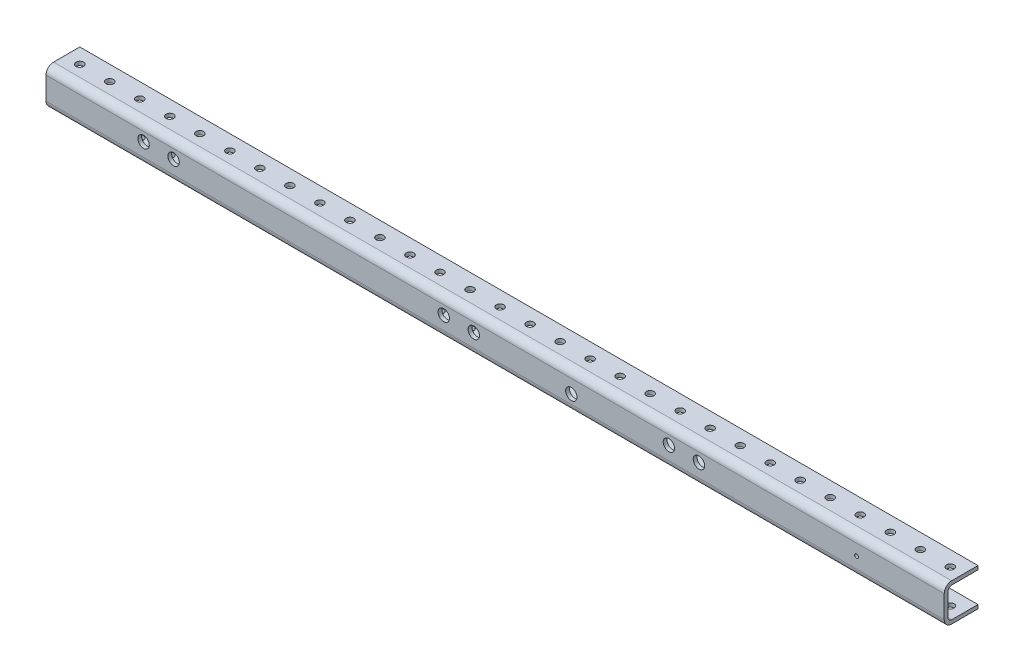
SolidWorks part; units mm, degrees
ref_plane "Front Plane" through (0, 0, 0) normal (0, 0, 1) x (1, 0, 0)
ref_plane "Top Plane" through (0, 0, 0) normal (0, 1, 0) x (1, 0, 0)
ref_plane "Right Plane" through (0, 0, 0) normal (1, 0, 0) x (0, 0, -1)
ref_plane "Plane1" through (0, 0, 3.175) normal (0, 0, 1) x (1, 0, 0)
sketch "Sketch1" plane through (0, 0, 3.175) normal (0, 0, 1) x (1, 0, 0)
  line L0 (872.98, -7.202) -> (872.98, 24.548)
  line L1 (872.98, 24.548) -> (-16.02, 24.548)
  line L2 (-16.02, 24.548) -> (-16.02, -7.202)
  line L3 (-16.02, -7.202) -> (872.98, -7.202)
extrude "Extrude1" add sketch "Sketch1" against normal blind 28.575
sketch "Sketch2" plane through (-16.02, 0, 0) normal (-1, 0, 0) x (0, 0, 1)
  line L0 (-25.4, 21.373) -> (-25.4, -4.027)
  line L1 (-25.4, -4.027) -> (0, -4.027)
  line L2 (0, -4.027) -> (0, 21.373)
  line L3 (0, 21.373) -> (-25.4, 21.373)
extrude "Extrude2" cut sketch "Sketch2" against normal up to next
hole_wizard "Hole1" positions "Sketch4" profile "Sketch3" legacy
sketch "Sketch4" plane through (0, 24.548, 0) normal (0, 1, 0) x (-1, 0, 0)
  point P0 (3.32, -12.7)
sketch "Sketch3" plane through (-3.32, 24.548, -12.7) normal (1, 0, 0) x (0, 0, 1)
  line L0 (0, 0) -> (0, 3.175)
  line L1 (0, 3.175) -> (3.175, 3.175)
  line L2 (3.175, 3.175) -> (3.175, 0)
  line L3 (3.175, 0) -> (0, 0)
  line L4 (0, 110) -> (0, -10) construction
  dimension "Diameter" = 6.35
  dimension "Depth" = 3.175
sketch3d "3DSketch1"
  point P0 (428.6664, 8.6668, -7.2024)
  point P1 (528.6664, 8.6668, -7.2024)
ref_axis "Axis1" through (528.6664, 8.6668, -7.2024) along (-1, 0, 0)
pattern_linear "LPattern1" count 35 spacing 25.4 along (1, 0, 0) of "Hole1"
hole_wizard "Hole2" positions "Sketch6" profile "Sketch5" legacy
sketch "Sketch6" plane through (0, 0, 3.175) normal (0, 0, 1) x (1, 0, 0)
  point P0 (66.53, 10.578)
sketch "Sketch5" plane through (66.53, 10.578, 3.175) normal (1, 0, 0) x (0, -1, 0)
  line L0 (0, 0) -> (0, 3.175)
  line L1 (0, 3.175) -> (4.826, 3.175)
  line L2 (4.826, 3.175) -> (4.826, 0)
  line L3 (4.826, 0) -> (0, 0)
  line L4 (0, 110) -> (0, -10) construction
  dimension "Diameter" = 9.652
  dimension "Depth" = 3.175
sketch3d "3DSketch2"
  point P0 (428.8468, 8.4517, -7.1294)
  point P1 (528.8468, 8.4517, -7.1294)
ref_axis "Axis2" through (528.8468, 8.4517, -7.1294) along (-1, 0, 0)
pattern_linear "LPattern2" count 12 spacing 25.4 along (1, 0, 0) skipping (2, 0), (3, 0), (4, 0), (5, 0), (6, 0), (7, 0), (8, 0), (9, 0) of "Hole2"
hole_wizard "Hole3" positions "Sketch8" profile "Sketch7" legacy
sketch "Sketch8" plane through (0, 0, 3.175) normal (0, 0, 1) x (1, 0, 0)
  point P0 (428.48, 6.768)
sketch "Sketch7" plane through (428.48, 6.768, 3.175) normal (1, 0, 0) x (0, -1, 0)
  line L0 (0, 0) -> (0, 3.175)
  line L1 (0, 3.175) -> (4.826, 3.175)
  line L2 (4.826, 3.175) -> (4.826, 0)
  line L3 (4.826, 0) -> (0, 0)
  line L4 (0, 110) -> (0, -10) construction
  dimension "Diameter" = 9.652
  dimension "Depth" = 3.175
hole_wizard "Hole4" positions "Sketch10" profile "Sketch9" legacy
sketch "Sketch10" plane through (0, 0, 3.175) normal (0, 0, 1) x (1, 0, 0)
  point P0 (511.03, 10.578)
sketch "Sketch9" plane through (511.03, 10.578, 3.175) normal (1, 0, 0) x (0, -1, 0)
  line L0 (0, 0) -> (0, 3.175)
  line L1 (0, 3.175) -> (4.826, 3.175)
  line L2 (4.826, 3.175) -> (4.826, 0)
  line L3 (4.826, 0) -> (0, 0)
  line L4 (0, 110) -> (0, -10) construction
  dimension "Diameter" = 9.652
  dimension "Depth" = 3.175
sketch3d "3DSketch3"
  point P0 (429.3014, 8.4448, -7.1738)
  point P1 (529.3014, 8.4448, -7.1738)
ref_axis "Axis3" through (529.3014, 8.4448, -7.1738) along (-1, 0, 0)
pattern_linear "LPattern3" count 12 spacing 25.4 along (1, 0, 0) skipping (2, 0), (3, 0), (4, 0), (5, 0), (6, 0), (7, 0), (8, 0), (9, 0) of "Hole4"
hole_wizard "Hole5" positions "Sketch12" profile "Sketch11" legacy
sketch "Sketch12" plane through (0, 0, 3.175) normal (0, 0, 1) x (1, 0, 0)
  point P0 (669.78, 8.673)
sketch "Sketch11" plane through (669.78, 8.673, 3.175) normal (1, 0, 0) x (0, -1, 0)
  line L0 (0, 0) -> (0, 3.175)
  line L1 (0, 3.175) -> (1.5875, 3.175)
  line L2 (1.5875, 3.175) -> (1.5875, 0)
  line L3 (1.5875, 0) -> (0, 0)
  line L4 (0, 110) -> (0, -10) construction
  dimension "Diameter" = 3.175
  dimension "Depth" = 3.175
hole_wizard "Hole6" positions "Sketch14" profile "Sketch13" legacy
sketch "Sketch14" plane through (0, -4.027, 0) normal (0, 1, 0) x (-1, 0, 0)
  point P0 (3.32, -12.7)
sketch "Sketch13" plane through (-3.32, -4.027, -12.7) normal (1, 0, 0) x (0, 0, 1)
  line L0 (0, 0) -> (0, 3.175)
  line L1 (0, 3.175) -> (3.175, 3.175)
  line L2 (3.175, 3.175) -> (3.175, 0)
  line L3 (3.175, 0) -> (0, 0)
  line L4 (0, 110) -> (0, -10) construction
  dimension "Diameter" = 6.35
  dimension "Depth" = 3.175
sketch3d "3DSketch4"
  point P0 (428.6444, 8.4444, -7.1991)
  point P1 (528.6444, 8.4444, -7.1991)
ref_axis "Axis4" through (528.6444, 8.4444, -7.1991) along (-1, 0, 0)
pattern_linear "LPattern4" count 35 spacing 25.4 along (1, 0, 0) of "Hole6"
fillet "Fillet1" radius 3.175 1 edges at (428.48, 21.373, 0) tangent propagation no
fillet "Fillet2" radius 3.175 1 edges at (428.48, -4.027, 0) tangent propagation no
fillet "Fillet3" radius 6.35 1 edges at (428.48, -7.202, 3.175) tangent propagation no
fillet "Fillet4" radius 6.35 1 edges at (428.48, 24.548, 3.175) tangent propagation no
sketch "Sketch15" plane through (0, 24.548, 0) normal (0, 1, 0) x (1, 0, 0)
  line L0 (-16.02, 14.2875) -> (743.98, 14.2875) construction
  line L1 (-16.02, 25.4) -> (-16.02, 3.175) construction
  line L3 (743.98, -10.6979) -> (876.3755, -10.6979)
  line L4 (743.98, -10.6979) -> (743.98, 49.9675)
  line L5 (743.98, 49.9675) -> (876.3755, 49.9675)
  line L6 (876.3755, -10.6979) -> (876.3755, 49.9675)
  dimension "D1" = 760
extrude "Cut-Extrude1" cut sketch "Sketch15" against normal through all
